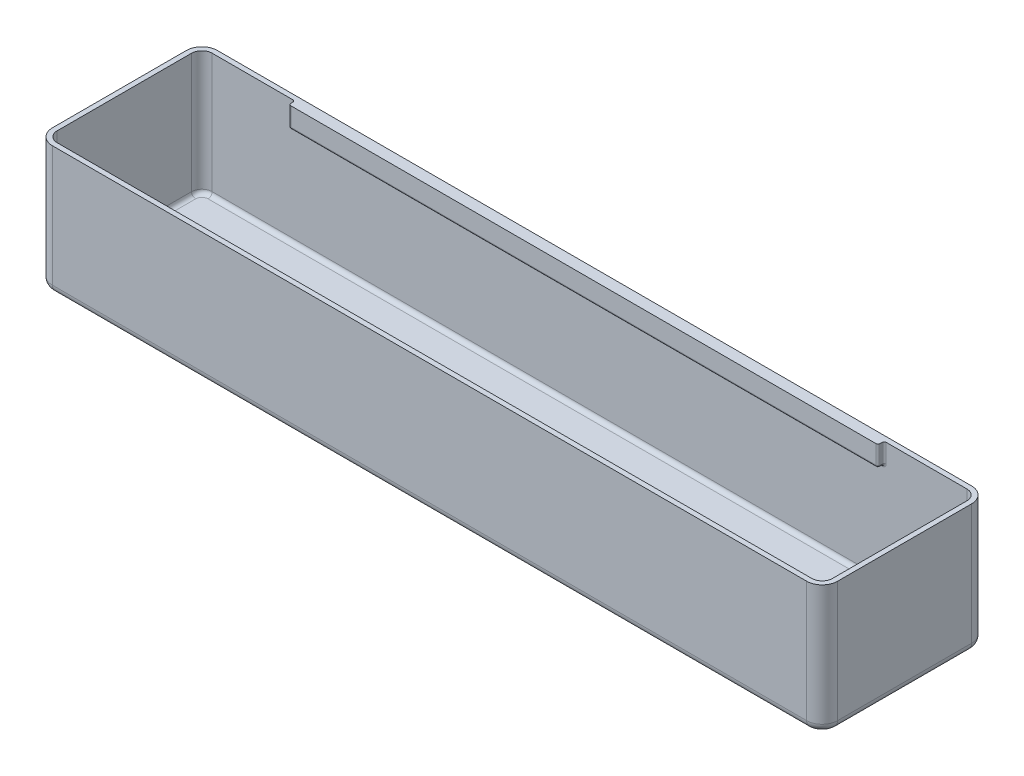
SolidWorks part; units mm, degrees
material "NEOPRENE"
ref_plane "Front" through (0, 0, 0) normal (0, 0, 1) x (1, 0, 0)
ref_plane "Top" through (0, 0, 0) normal (0, 1, 0) x (1, 0, 0)
ref_plane "Right" through (0, 0, 0) normal (1, 0, 0) x (0, 0, -1)
sketch "Sketch1" plane through (0, 0, 0) normal (0, 1, 0) x (1, 0, 0)
  line L0 (-119.0625, 0) -> (-120.5865, 0) construction
  line L1 (-120.5865, 25.3365) -> (120.5865, 25.3365)
  line L2 (-120.5865, 25.3365) -> (-120.5865, -25.3365)
  line L3 (-120.5865, -25.3365) -> (120.5865, -25.3365)
  line L4 (120.5865, 25.3365) -> (120.5865, -25.3365)
  line L5 (-120.5865, 25.3365) -> (120.5865, -25.3365) construction
  line L6 (-120.5865, -25.3365) -> (120.5865, 25.3365) construction
  line L7 (119.0625, 23.8125) -> (-119.0625, 23.8125)
  line L8 (119.0625, 23.8125) -> (119.0625, -23.8125)
  line L9 (119.0625, -23.8125) -> (-119.0625, -23.8125)
  line L10 (-119.0625, 23.8125) -> (-119.0625, -23.8125)
  line L11 (119.0625, 23.8125) -> (-119.0625, -23.8125) construction
  line L12 (119.0625, -23.8125) -> (-119.0625, 23.8125) construction
  line L13 (0, 23.8125) -> (0, 25.3365) construction
  point P0 (0, 0)
  point P6 (0, 0)
  dimension "D1" = 238.125
  dimension "D2" = 47.625
  dimension "THICKNESS" = 1.524
extrude "Boss-Extrude1" add sketch "Sketch1" along normal blind 38.1
sketch "Sketch2" plane through (0, 0, 0) normal (0, -1, 0) x (1, 0, 0)
  line L4 (120.5865, -25.3365) -> (120.5865, 25.3365)
  line L5 (120.5865, 25.3365) -> (-120.5865, 25.3365)
  line L6 (-120.5865, 25.3365) -> (-120.5865, -25.3365)
  line L7 (-120.5865, -25.3365) -> (120.5865, -25.3365)
  line L8 (120.5865, -25.3365) -> (120.5865, 25.3365)
  line L9 (120.5865, 25.3365) -> (-120.5865, 25.3365)
  line L10 (-120.5865, 25.3365) -> (-120.5865, -25.3365)
  line L11 (-120.5865, -25.3365) -> (120.5865, -25.3365)
  arc A0 (104.3365, 1.0115) -> (104.3365, 5.2115) centre (104.3365, 3.1115) ccw construction
  arc A1 (104.3365, 5.2115) -> (104.3365, 1.0115) centre (104.3365, 3.1115) ccw construction
  arc A2 (73.3365, 1.0115) -> (73.3365, 5.2115) centre (73.3365, 3.1115) ccw construction
  arc A3 (73.3365, 5.2115) -> (73.3365, 1.0115) centre (73.3365, 3.1115) ccw construction
  arc A4 (104.3365, 1.0115) -> (104.3365, 5.2115) centre (104.3365, 3.1115) ccw
  arc A5 (104.3365, 5.2115) -> (104.3365, 1.0115) centre (104.3365, 3.1115) ccw
  arc A6 (73.3365, 1.0115) -> (73.3365, 5.2115) centre (73.3365, 3.1115) ccw
  arc A7 (73.3365, 5.2115) -> (73.3365, 1.0115) centre (73.3365, 3.1115) ccw
  dimension "D1" = 0
extrude "Boss-Extrude2" add sketch "Sketch2" along normal blind 1.524
fillet "Fillet1" radius 3.175 4 edges at (119.0625, 19.05, -23.8125) (119.0625, 19.05, 23.8125) (-119.0625, 19.05, 23.8125) (-119.0625, 19.05, -23.8125)
fillet "Fillet2" radius 4.7625 4 edges at (-120.5865, 18.288, -25.3365) (120.5865, 18.288, -25.3365) (120.5865, 18.288, 25.3365) (-120.5865, 18.288, 25.3365)
sketch "Sketch4" plane through (0, -1.524, 0) normal (0, -1, 0) x (1, 0, 0)
  line L2 (120.5865, -20.574) -> (120.5865, 20.574) construction
  line L3 (115.824, 25.3365) -> (-115.824, 25.3365) construction
  circle A0 centre (88.8365, 3.1115) radius 12.065
  dimension "D1" = 24.13
  dimension "D3" = 22.225
  dimension "D2" = 31.75
extrude "Cut-Extrude2" cut sketch "Sketch4" against normal through all
sketch "Sketch5" plane through (0, 0, -23.8125) normal (0, 0, 1) x (1, 0, 0)
  line L0 (0, 0) -> (0, 34.925) construction
  line L1 (115.8875, 38.1) -> (-115.8875, 38.1) construction
  line L2 (-90.4875, 31.75) -> (90.4875, 31.75)
  line L3 (-90.4875, 31.75) -> (-90.4875, 38.1)
  line L4 (-90.4875, 38.1) -> (90.4875, 38.1)
  line L5 (90.4875, 31.75) -> (90.4875, 38.1)
  line L6 (-90.4875, 31.75) -> (90.4875, 38.1) construction
  line L7 (-90.4875, 38.1) -> (90.4875, 31.75) construction
  dimension "D1" = 180.975
  dimension "D2" = 6.35
extrude "Boss-Extrude3" add sketch "Sketch5" along normal blind 1.905
fillet "Fillet3" radius 0.635 8 edges at (0, 31.75, -21.9075) (0, 31.75, -23.8125) (-90.4875, 34.925, -23.8125) (-90.4875, 34.925, -21.9075) (90.4875, 34.925, -21.9075) (90.4875, 34.925, -23.8125) (-90.4875, 31.75, -22.86) (90.4875, 31.75, -22.86)
fillet "Fillet4" radius 1.27 8 edges at (118.1326, 0, -22.8826) (119.0625, 0, 0) (118.1326, 0, 22.8826) (0, 0, 23.8125) (-118.1326, 0, 22.8826) (-119.0625, 0, 0) (-118.1326, 0, -22.8826) (0, 0, -23.8125)
fillet "Fillet5" radius 2.54 8 edges at (-119.1916, -1.524, 23.9416) (0, -1.524, 25.3365) (119.1916, -1.524, 23.9416) (120.5865, -1.524, 0) (119.1916, -1.524, -23.9416) (0, -1.524, -25.3365) (-119.1916, -1.524, -23.9416) (-120.5865, -1.524, 0)
sketch "Sketch6" [suppressed] plane through (0, -1.524, 0) normal (0, -1, 0) x (1, 0, 0)
  circle A0 centre (73.3365, 3.1115) radius 2.1 construction
  circle A1 centre (73.3365, 3.1115) radius 2.1
  circle A2 centre (104.3365, 3.1115) radius 2.1 construction
  circle A3 centre (104.3365, 3.1115) radius 2.1
extrude "Boss-Extrude4" [suppressed] add sketch "Sketch6" against normal up to surface (1.524 mm away) up to face at (0, 0, 0)
sketch "Sketch7" [suppressed] plane through (0, -1.524, 0) normal (0, -1, 0) x (1, 0, 0)
  circle A0 centre (-45.2, 0.936) radius 12.192
  circle A1 centre (45, 0.936) radius 12.192
  dimension "D1" = 24.384
extrude "Cut-Extrude3" [suppressed] cut sketch "Sketch7" against normal through all
equation "\"D1@Boss-Extrude2\"=\"THICKNESS\""
